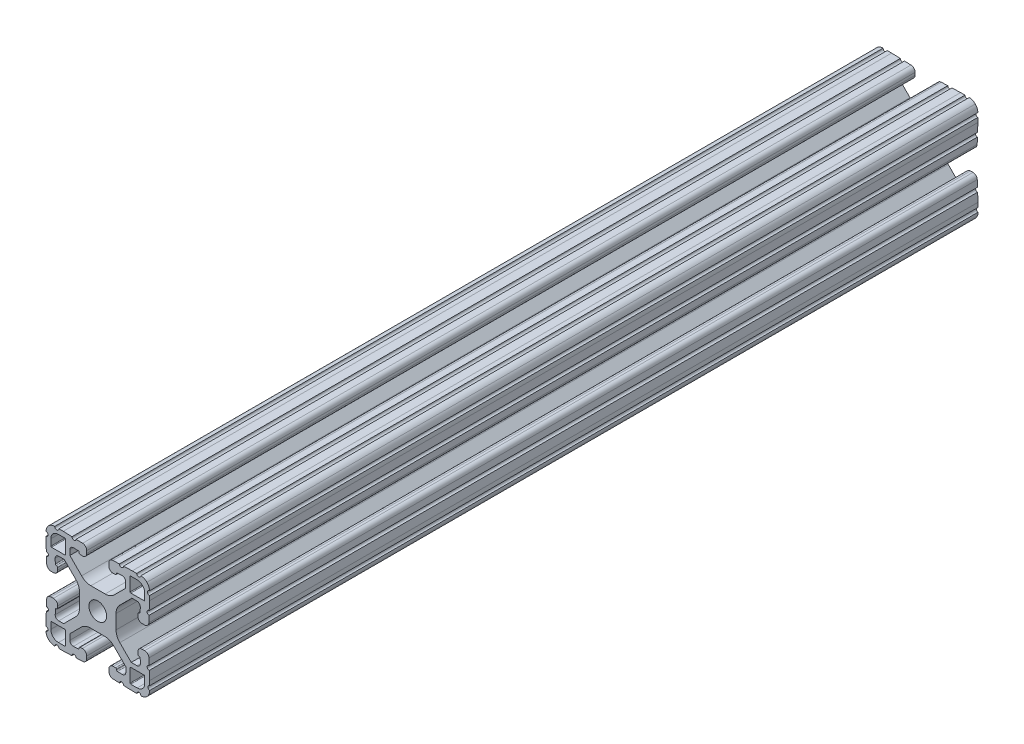
SolidWorks part; units mm, degrees
material "6061-T6 (SS)"
ref_plane "Front Plane" through (0, 0, 0) normal (0, 0, 1) x (1, 0, 0)
ref_plane "Top Plane" through (0, 0, 0) normal (0, 1, 0) x (1, 0, 0)
ref_plane "Right Plane" through (0, 0, 0) normal (1, 0, 0) x (0, 0, -1)
ref_plane "Plane1" through (0, 0, -25.4) normal (0, 0, -1) x (-1, 0, 0)
sketch "Sketch1" plane through (0, 0, -25.4) normal (0, 0, -1) x (-1, 0, 0)
  line L0 (-83.3577, 88.2941) -> (-83.3577, 93.1709)
  line L1 (-83.1037, 93.4249) -> (-80.767, 93.4249)
  line L2 (-77.9729, 90.6309) -> (-77.9729, 88.2941)
  line L3 (-78.2269, 88.0401) -> (-83.1037, 88.0401)
  line L4 (-83.3577, 59.2291) -> (-83.3577, 64.1059)
  line L5 (-83.1037, 64.3599) -> (-78.2269, 64.3599)
  line L6 (-77.9729, 64.1059) -> (-77.9729, 61.7691)
  line L7 (-80.767, 58.9751) -> (-83.1037, 58.9751)
  line L8 (-107.1423, 93.1709) -> (-107.1423, 88.2941)
  line L9 (-107.3963, 88.0401) -> (-112.2731, 88.0401)
  line L10 (-112.5271, 88.2941) -> (-112.5271, 90.6309)
  line L11 (-109.733, 93.4249) -> (-107.3963, 93.4249)
  line L12 (-107.1423, 64.1059) -> (-107.1423, 59.2291)
  line L13 (-107.3963, 58.9751) -> (-109.733, 58.9751)
  line L14 (-112.5271, 61.7691) -> (-112.5271, 64.1059)
  line L15 (-112.2731, 64.3599) -> (-107.3963, 64.3599)
  line L16 (-88.0437, 91.8626) -> (-86.2967, 91.9236)
  line L17 (-84.9824, 90.6544) -> (-84.9824, 88.8002)
  line L18 (-84.9824, 88.8002) -> (-89.3066, 84.476)
  line L19 (-92.7196, 83.0295) -> (-97.9616, 83.0295)
  line L20 (-101.3202, 84.4207) -> (-105.516, 88.6165)
  line L21 (-105.516, 88.6165) -> (-105.516, 90.7313)
  line L22 (-104.2017, 92.0006) -> (-102.4547, 91.9396)
  line L23 (-101.7262, 91.1059) -> (-100.9297, 91.0781)
  line L24 (-99.2999, 92.6519) -> (-99.2999, 93.5668)
  line L25 (-100.8197, 95.1407) -> (-103.2119, 95.2242)
  line L26 (-104.735, 95.2774) -> (-107.9359, 95.3892)
  line L27 (-107.9359, 95.3892) -> (-109.5615, 95.3892)
  line L28 (-114.2859, 90.6648) -> (-114.2859, 89.0392)
  line L29 (-114.2859, 89.0392) -> (-114.1741, 85.8383)
  line L30 (-114.1209, 84.3152) -> (-114.0374, 81.9231)
  line L31 (-112.4635, 80.4032) -> (-111.5486, 80.4032)
  line L32 (-109.9748, 82.033) -> (-110.0026, 82.8295)
  line L33 (-110.8377, 83.5577) -> (-110.8987, 85.3047)
  line L34 (-109.6294, 86.619) -> (-107.8072, 86.619)
  line L35 (-107.8072, 86.619) -> (-103.3649, 82.1768)
  line L36 (-101.9737, 78.8182) -> (-101.9737, 73.576)
  line L37 (-103.3649, 70.2174) -> (-107.5607, 66.0217)
  line L38 (-107.5607, 66.0217) -> (-109.6524, 66.0217)
  line L39 (-110.9217, 67.336) -> (-110.8607, 69.083)
  line L40 (-110.0322, 69.8124) -> (-110.0043, 70.6089)
  line L41 (-111.5782, 72.2387) -> (-112.4931, 72.2387)
  line L42 (-114.0669, 70.7189) -> (-114.1505, 68.3267)
  line L43 (-114.2036, 66.8036) -> (-114.3154, 63.6027)
  line L44 (-114.3154, 63.6027) -> (-114.3154, 61.9626)
  line L45 (-109.6111, 57.1437) -> (-107.9855, 57.1437)
  line L46 (-107.9855, 57.1437) -> (-104.7846, 57.2555)
  line L47 (-103.2615, 57.3086) -> (-100.8694, 57.3922)
  line L48 (-99.3495, 58.966) -> (-99.3495, 59.8809)
  line L49 (-100.9794, 61.4548) -> (-101.7758, 61.4269)
  line L50 (-102.5054, 60.599) -> (-104.2524, 60.538)
  line L51 (-105.5667, 61.8072) -> (-105.5667, 63.6295)
  line L52 (-105.5667, 63.6295) -> (-101.1311, 68.065)
  line L53 (-97.7725, 69.4562) -> (-92.5304, 69.4562)
  line L54 (-89.1717, 68.065) -> (-84.976, 63.8692)
  line L55 (-84.976, 63.8692) -> (-84.976, 61.7811)
  line L56 (-86.2903, 60.5118) -> (-88.0373, 60.5728)
  line L57 (-88.7596, 61.4332) -> (-89.5561, 61.461)
  line L58 (-91.1859, 59.8872) -> (-91.1859, 58.9723)
  line L59 (-89.6661, 57.3985) -> (-87.2739, 57.3149)
  line L60 (-85.7508, 57.2617) -> (-82.5499, 57.15)
  line L61 (-82.5499, 57.15) -> (-80.9244, 57.15)
  line L62 (-76.2, 61.8744) -> (-76.2, 63.4999)
  line L63 (-76.2, 63.4999) -> (-76.3117, 66.7008)
  line L64 (-76.3649, 68.2239) -> (-76.4484, 70.6161)
  line L65 (-78.0223, 72.1359) -> (-78.9372, 72.1359)
  line L66 (-80.511, 70.5061) -> (-80.4832, 69.7096)
  line L67 (-79.6552, 68.9801) -> (-79.5942, 67.2331)
  line L68 (-80.8634, 65.9188) -> (-82.6857, 65.9188)
  line L69 (-82.6857, 65.9188) -> (-87.1213, 70.3543)
  line L70 (-88.5125, 73.7128) -> (-88.5126, 78.955)
  line L71 (-87.1214, 82.3137) -> (-82.9257, 86.5095)
  line L72 (-82.9257, 86.5095) -> (-80.8375, 86.5095)
  line L73 (-79.5682, 85.1951) -> (-79.6293, 83.4482)
  line L74 (-80.4896, 82.7258) -> (-80.5175, 81.9294)
  line L75 (-78.9436, 80.2995) -> (-78.0287, 80.2995)
  line L76 (-76.4549, 81.8194) -> (-76.3713, 84.2115)
  line L77 (-76.3182, 85.7346) -> (-76.2064, 88.9355)
  line L78 (-76.2064, 88.9355) -> (-76.2064, 90.5611)
  line L79 (-80.9308, 95.2855) -> (-82.5564, 95.2855)
  line L80 (-82.5564, 95.2855) -> (-85.7573, 95.1737)
  line L81 (-87.2803, 95.1205) -> (-89.6725, 95.037)
  line L82 (-91.1924, 93.4632) -> (-91.1924, 92.5483)
  line L83 (-89.5625, 90.9744) -> (-88.7661, 91.0023)
  arc A0 (-83.3577, 93.1709) -> (-83.1037, 93.4249) centre (-83.1037, 93.1709) cw
  arc A1 (-80.767, 93.4249) -> (-77.9729, 90.6309) centre (-80.7669, 90.6309) cw
  arc A2 (-77.9729, 88.2941) -> (-78.2269, 88.0401) centre (-78.2269, 88.2941) cw
  arc A3 (-83.1037, 88.0401) -> (-83.3577, 88.2941) centre (-83.1037, 88.2941) cw
  arc A4 (-83.1037, 58.9751) -> (-83.3577, 59.2291) centre (-83.1037, 59.2291) cw
  arc A5 (-83.3577, 64.1059) -> (-83.1037, 64.3599) centre (-83.1037, 64.1059) cw
  arc A6 (-78.2269, 64.3599) -> (-77.9729, 64.1059) centre (-78.2269, 64.1059) cw
  arc A7 (-77.9729, 61.7691) -> (-80.767, 58.9751) centre (-80.7669, 61.7691) cw
  arc A8 (-107.3963, 93.4249) -> (-107.1423, 93.1709) centre (-107.3963, 93.1709) cw
  arc A9 (-107.1423, 88.2941) -> (-107.3963, 88.0401) centre (-107.3963, 88.2941) cw
  arc A10 (-112.2731, 88.0401) -> (-112.5271, 88.2941) centre (-112.2731, 88.2941) cw
  arc A11 (-112.5271, 90.6309) -> (-109.733, 93.4249) centre (-109.7331, 90.6309) cw
  arc A12 (-107.1423, 59.2291) -> (-107.3963, 58.9751) centre (-107.3963, 59.2291) cw
  arc A13 (-109.733, 58.9751) -> (-112.5271, 61.7691) centre (-109.7331, 61.7691) cw
  arc A14 (-112.5271, 64.1059) -> (-112.2731, 64.3599) centre (-112.2731, 64.1059) cw
  arc A15 (-107.3963, 64.3599) -> (-107.1423, 64.1059) centre (-107.3963, 64.1059) cw
  circle A16 centre (-95.25, 76.2) radius 3.2639
  arc A17 (-88.7661, 91.0023) -> (-88.3984, 91.383) centre (-88.7794, 91.383) ccw
  arc A18 (-88.3984, 91.383) -> (-88.0437, 91.8626) centre (-88.0304, 91.4819) cw
  arc A19 (-86.2967, 91.9236) -> (-84.9824, 90.6544) centre (-86.2524, 90.6544) cw
  arc A20 (-89.3066, 84.476) -> (-92.7196, 83.0295) centre (-92.7196, 87.7793) cw
  arc A21 (-97.9616, 83.0295) -> (-101.3202, 84.4207) centre (-97.9616, 87.7793) cw
  arc A22 (-105.516, 90.7313) -> (-104.2017, 92.0006) centre (-104.246, 90.7313) cw
  arc A23 (-102.4547, 91.9396) -> (-102.087, 91.5588) centre (-102.468, 91.5588) cw
  arc A24 (-102.087, 91.5588) -> (-101.7262, 91.1059) centre (-101.7129, 91.4867) ccw
  arc A25 (-100.9297, 91.0781) -> (-99.2999, 92.6519) centre (-100.8747, 92.6519) ccw
  arc A26 (-99.2999, 93.5668) -> (-100.8197, 95.1407) centre (-100.8747, 93.5668) ccw
  arc A27 (-103.2119, 95.2242) -> (-104.735, 95.2774) centre (-103.9735, 95.2508) cw
  arc A28 (-109.5615, 95.3892) -> (-111.0855, 95.3892) centre (-110.3235, 95.3892) cw
  arc A29 (-111.0855, 95.3892) -> (-113.3432, 94.4465) centre (-111.0855, 92.2142) ccw
  arc A30 (-113.3432, 94.4465) -> (-114.2859, 92.1888) centre (-111.1109, 92.1888) ccw
  arc A31 (-114.2859, 92.1888) -> (-114.2859, 90.6648) centre (-114.2859, 91.4268) cw
  arc A32 (-114.1741, 85.8383) -> (-114.1209, 84.3152) centre (-114.1475, 85.0768) cw
  arc A33 (-114.0374, 81.9231) -> (-112.4635, 80.4032) centre (-112.4635, 81.978) ccw
  arc A34 (-111.5486, 80.4032) -> (-109.9748, 82.033) centre (-111.5486, 81.978) ccw
  arc A35 (-110.0026, 82.8295) -> (-110.3834, 83.1972) centre (-110.3834, 82.8162) ccw
  arc A36 (-110.3834, 83.1972) -> (-110.8377, 83.5577) centre (-110.4569, 83.571) cw
  arc A37 (-110.8987, 85.3047) -> (-109.6294, 86.619) centre (-109.6294, 85.349) cw
  arc A38 (-103.3649, 82.1768) -> (-101.9737, 78.8182) centre (-106.7235, 78.8182) cw
  arc A39 (-101.9737, 73.576) -> (-103.3649, 70.2174) centre (-106.7235, 73.576) cw
  arc A40 (-109.6524, 66.0217) -> (-110.9217, 67.336) centre (-109.6524, 67.2917) cw
  arc A41 (-110.8607, 69.083) -> (-110.4799, 69.4507) centre (-110.4799, 69.0697) cw
  arc A42 (-110.4799, 69.4507) -> (-110.0322, 69.8124) centre (-110.413, 69.8257) ccw
  arc A43 (-110.0043, 70.6089) -> (-111.5782, 72.2387) centre (-111.5782, 70.6639) ccw
  arc A44 (-112.4931, 72.2387) -> (-114.0669, 70.7189) centre (-112.4931, 70.6639) ccw
  arc A45 (-114.1505, 68.3267) -> (-114.2036, 66.8036) centre (-114.1771, 67.5652) cw
  arc A46 (-114.3154, 61.9626) -> (-114.3332, 60.4644) centre (-114.4639, 61.2152) cw
  arc A47 (-114.3332, 60.4644) -> (-113.3928, 58.0864) centre (-111.1605, 60.3441) ccw
  arc A48 (-113.3928, 58.0864) -> (-111.1351, 57.1437) centre (-111.1351, 60.3187) ccw
  arc A49 (-111.1351, 57.1437) -> (-109.6111, 57.1437) centre (-110.3731, 57.1437) cw
  arc A50 (-104.7846, 57.2555) -> (-103.2615, 57.3086) centre (-104.0231, 57.2821) cw
  arc A51 (-100.8694, 57.3922) -> (-99.3495, 58.966) centre (-100.9243, 58.966) ccw
  arc A52 (-99.3495, 59.8809) -> (-100.9794, 61.4548) centre (-100.9243, 59.8809) ccw
  arc A53 (-101.7758, 61.4269) -> (-102.1435, 61.0462) centre (-101.7625, 61.0462) ccw
  arc A54 (-102.1435, 61.0462) -> (-102.5054, 60.599) centre (-102.5187, 60.9797) cw
  arc A55 (-104.2524, 60.538) -> (-105.5667, 61.8072) centre (-104.2967, 61.8072) cw
  arc A56 (-101.1311, 68.065) -> (-97.7725, 69.4562) centre (-97.7725, 64.7064) cw
  arc A57 (-92.5304, 69.4562) -> (-89.1717, 68.065) centre (-92.5304, 64.7064) cw
  arc A58 (-84.976, 61.7811) -> (-86.2903, 60.5118) centre (-86.246, 61.7811) cw
  arc A59 (-88.0373, 60.5728) -> (-88.405, 60.9536) centre (-88.024, 60.9536) cw
  arc A60 (-88.405, 60.9536) -> (-88.7596, 61.4332) centre (-88.7729, 61.0524) ccw
  arc A61 (-89.5561, 61.461) -> (-91.1859, 59.8872) centre (-89.6111, 59.8872) ccw
  arc A62 (-91.1859, 58.9723) -> (-89.6661, 57.3985) centre (-89.6111, 58.9723) ccw
  arc A63 (-87.2739, 57.3149) -> (-85.7508, 57.2617) centre (-86.5124, 57.2883) cw
  arc A64 (-80.9244, 57.15) -> (-79.4004, 57.15) centre (-80.1624, 57.15) cw
  arc A65 (-79.4004, 57.15) -> (-77.1426, 58.0927) centre (-79.4004, 60.325) ccw
  arc A66 (-77.1426, 58.0927) -> (-76.2, 60.3504) centre (-79.375, 60.3504) ccw
  arc A67 (-76.2, 60.3504) -> (-76.2, 61.8744) centre (-76.2, 61.1124) cw
  arc A68 (-76.3117, 66.7008) -> (-76.3649, 68.2239) centre (-76.3383, 67.4624) cw
  arc A69 (-76.4484, 70.6161) -> (-78.0223, 72.1359) centre (-78.0223, 70.5611) ccw
  arc A70 (-78.9372, 72.1359) -> (-80.511, 70.5061) centre (-78.9372, 70.5611) ccw
  arc A71 (-80.4832, 69.7096) -> (-80.1024, 69.342) centre (-80.1024, 69.723) ccw
  arc A72 (-80.1024, 69.342) -> (-79.6552, 68.9801) centre (-80.036, 68.9668) cw
  arc A73 (-79.5942, 67.2331) -> (-80.8634, 65.9188) centre (-80.8634, 67.1888) cw
  arc A74 (-87.1213, 70.3543) -> (-88.5125, 73.7128) centre (-83.7627, 73.7129) cw
  arc A75 (-88.5126, 78.955) -> (-87.1214, 82.3137) centre (-83.7628, 78.9551) cw
  arc A76 (-80.8375, 86.5095) -> (-79.5682, 85.1951) centre (-80.8375, 85.2395) cw
  arc A77 (-79.6293, 83.4482) -> (-80.01, 83.0805) centre (-80.01, 83.4615) cw
  arc A78 (-80.01, 83.0805) -> (-80.4896, 82.7258) centre (-80.1089, 82.7125) ccw
  arc A79 (-80.5175, 81.9294) -> (-78.9436, 80.2995) centre (-78.9436, 81.8743) ccw
  arc A80 (-78.0287, 80.2995) -> (-76.4549, 81.8194) centre (-78.0287, 81.8743) ccw
  arc A81 (-76.3713, 84.2115) -> (-76.3182, 85.7346) centre (-76.3448, 84.9731) cw
  arc A82 (-76.2064, 90.5611) -> (-76.2064, 92.0851) centre (-76.2064, 91.3231) cw
  arc A83 (-76.2064, 92.0851) -> (-77.1491, 94.3428) centre (-79.3814, 92.0851) ccw
  arc A84 (-77.1491, 94.3428) -> (-79.4068, 95.2855) centre (-79.4068, 92.1105) ccw
  arc A85 (-79.4068, 95.2855) -> (-80.9308, 95.2855) centre (-80.1688, 95.2855) cw
  arc A86 (-85.7573, 95.1737) -> (-87.2803, 95.1205) centre (-86.5188, 95.1471) cw
  arc A87 (-89.6725, 95.037) -> (-91.1924, 93.4632) centre (-89.6176, 93.4632) ccw
  arc A88 (-91.1924, 92.5483) -> (-89.5625, 90.9744) centre (-89.6176, 92.5483) ccw
extrude "Boss-Extrude1" add sketch "Sketch1" against normal blind 304.8
